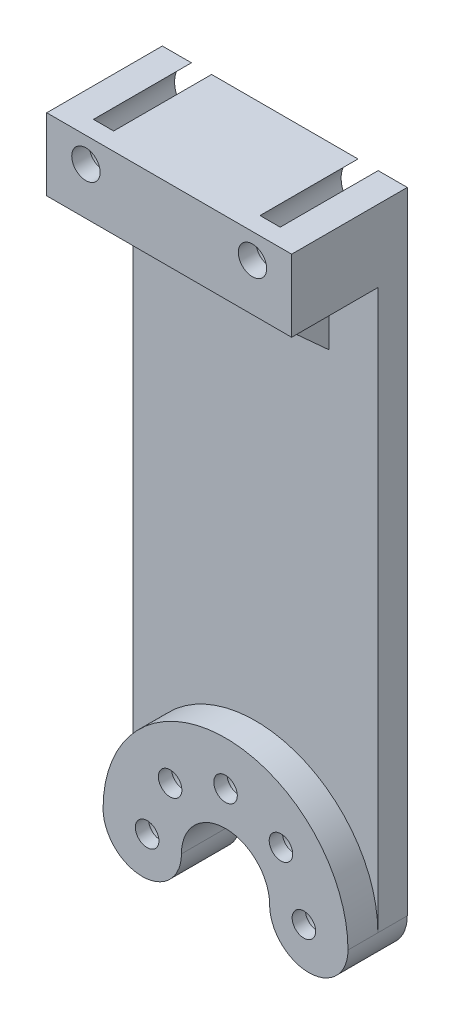
SolidWorks part; units mm, degrees
ref_plane "Plano frontal" through (0, 0, 0) normal (0, 0, 1) x (1, 0, 0)
ref_plane "Plano superior" through (0, 0, 0) normal (0, 1, 0) x (1, 0, 0)
ref_plane "Plano direito" through (0, 0, 0) normal (1, 0, 0) x (0, 0, -1)
sketch "Esboço1" plane through (0, 0, 0) normal (0, 0, 1) x (1, 0, 0)
  arc A0 (4.5, 0) -> (-4.5, 0) centre (0, 0) ccw
  arc A1 (12.5, 0) -> (-12.5, 0) centre (0, 0) ccw
  arc A2 (12.5, 0) -> (4.5, 0) centre (8.5, 0) cw
  arc A3 (-4.5, 0) -> (-12.5, 0) centre (-8.5, 0) cw
  arc A4 (4, 0) -> (-4, 0) centre (0, 0) ccw construction
  circle A6 centre (8.5, 61.8383) radius 1.35 construction
  dimension "D1" = 0.5
  dimension "D2" = 4
extrude "Ressalto-extrusão1" add sketch "Esboço1" against normal offset from surface (3.05 mm away) 2 offset beyond the face yes
sketch "Esboço2" plane through (0, 0, -3.05) normal (0, 0, -1) x (-1, 0, 0)
  line L1 (-12.5, 64.3883) -> (12.5, 64.3883)
  line L3 (9.2, 64.6383) -> (-9.2, 64.6383) construction
  line L6 (-12.5, 64.3883) -> (-12.5, 0)
  line L9 (12.5, 64.3883) -> (12.5, 0)
  arc A6 (4.5, 0) -> (12.5, 0) centre (8.5, 0) ccw construction
  arc A7 (-12.5, 0) -> (-4.5, 0) centre (-8.5, 0) ccw construction
  arc A8 (4.5, 0) -> (12.5, 0) centre (8.5, 0) ccw
  arc A9 (-12.5, 0) -> (-4.5, 0) centre (-8.5, 0) ccw
  arc A13 (4.5, 0) -> (-4.5, 0) centre (0, 0) ccw construction
  arc A16 (4.5, 0) -> (-4.5, 0) centre (0, 0) ccw
  dimension "D3" = 0.25
extrude "Ressalto-extrusão2" add sketch "Esboço2" along normal blind 3
sketch "Esboço4" plane through (0, 0, -6.05) normal (0, 0, -1) x (-1, 0, 0)
  line L1 (-12.5, 64.3883) -> (12.5, 64.3883)
  line L2 (-12.5, 64.3883) -> (-12.5, 57.0383)
  line L3 (-12.5, 57.0383) -> (12.5, 57.0383)
  line L4 (12.5, 64.3883) -> (12.5, 57.0383)
  line L5 (12.5, 0) -> (12.5, 64.3883) construction
  line L6 (-12.7, 59.0383) -> (12.7, 59.0383) construction
  dimension "D1" = 2
extrude "Ressalto-extrusão3" add sketch "Esboço4" against normal up to surface (11.8 mm away)
hole_wizard "Rebaixo para SHCS M2.51" positions "Sketch1" profile "Sketch2" counterbore size "M2.5" standard "Ansi Metric" end condition up to next
sketch "Sketch1" plane through (0, 0, -6.05) normal (0, 0, -1) x (-1, 0, 0)
  circle A0 centre (-8.5, 61.8383) radius 1.35 construction
  circle A1 centre (8.5, 61.8383) radius 1.35 construction
  point P0 (-8.5, 61.8383)
  point P3 (8.5, 61.8383)
sketch "Sketch2" plane through (8.5, 61.8383, -6.05) normal (1, 0, 0) x (0, 1, 0)
  line L0 (0, 0) -> (0, 11.8)
  line L1 (0, 11.8) -> (1.45, 11.8)
  line L3 (1.45, 11.8) -> (1.45, 10)
  line L4 (1.45, 10) -> (2.75, 10)
  line L5 (2.75, 10) -> (2.75, 0)
  line L7 (2.75, 0) -> (0, 0)
  line L11 (0, -6.35) -> (0, 107.95) construction
  dimension "Thru Hole Dia." = 2.9
  dimension "Thru Hole Depth" = 11.8
  dimension "C'Bore Dia." = 5.5
  dimension "C'Bore Depth" = 10
hole_wizard "Rebaixo para SHCS M21" positions "Sketch3" profile "Sketch4" counterbore size "M2" standard "Ansi Metric" end condition up to next
sketch "Sketch3" plane through (0, 0, -6.05) normal (0, 0, -1) x (-1, 0, 0)
  line L0 (0, 0) -> (-8, 0) construction
  line L1 (0, 0) -> (-5.6569, 5.6569) construction
  line L2 (0, 0) -> (0, 8) construction
  line L3 (0, 0) -> (5.6569, 5.6569) construction
  line L4 (0, 0) -> (8, 0) construction
  arc A0 (-8.8, 0) -> (-7.2, 0) centre (-8, 0) ccw construction
  point P0 (-8, 0)
  point P15 (-5.6569, 5.6569)
  point P17 (0, 8)
  point P19 (5.6569, 5.6569)
  point P21 (8, 0)
  dimension "D1" = 5
sketch "Sketch4" plane through (8, 0, -6.05) normal (1, 0, 0) x (0, 1, 0)
  line L0 (0, 0) -> (0, 6.05)
  line L1 (0, 6.05) -> (1.2, 6.05)
  line L3 (1.2, 6.05) -> (1.2, 4.7)
  line L4 (1.2, 4.7) -> (2.2, 4.7)
  line L5 (2.2, 4.7) -> (2.2, 0)
  line L7 (2.2, 0) -> (0, 0)
  line L11 (0, -6.35) -> (0, 107.95) construction
  dimension "Thru Hole Dia." = 2.4
  dimension "Thru Hole Depth" = 6.05
  dimension "C'Bore Dia." = 4.4
  dimension "C'Bore Depth" = 4.7
sketch "Esboço5" plane through (0, 0, 0) normal (1, 0, 0) x (0, 0, -1)
  line L0 (-5.75, 57.0383) -> (3.05, 49.0383)
  line L1 (3.05, 57.0383) -> (3.05, 0) construction
  line L2 (-5.75, 57.0383) -> (3.05, 57.0383) construction
  dimension "D1" = 8
rib "Nervura1" sketch "Esboço5" sketch "Esboço5" thickness 15 extrusion direction parallel to sketch draft on no parameters "D1"=15
sketch "Esboço6" plane through (0, 0, -3.05) normal (0, 0, 1) x (1, 0, 0)
  line L0 (7.5, 49.0383) -> (-7.5, 49.0383) construction
  line L1 (4.4016, 49.0383) -> (-4.5372, 49.0383)
  line L2 (4.4016, 49.0383) -> (4.4016, 57.0383)
  line L3 (4.4016, 57.0383) -> (-4.5372, 57.0383)
  line L4 (-4.5372, 49.0383) -> (-4.5372, 57.0383)
  line L5 (4.4635, 57.1) -> (4.4021, 49.1002) construction
  line L6 (-7.5, 57.0383) -> (7.5, 57.0383) construction
  line L7 (-4.5976, 49.1693) -> (-4.5362, 57.1691) construction
extrude "Corte-extrusão1" cut sketch "Esboço6" along normal up to next
